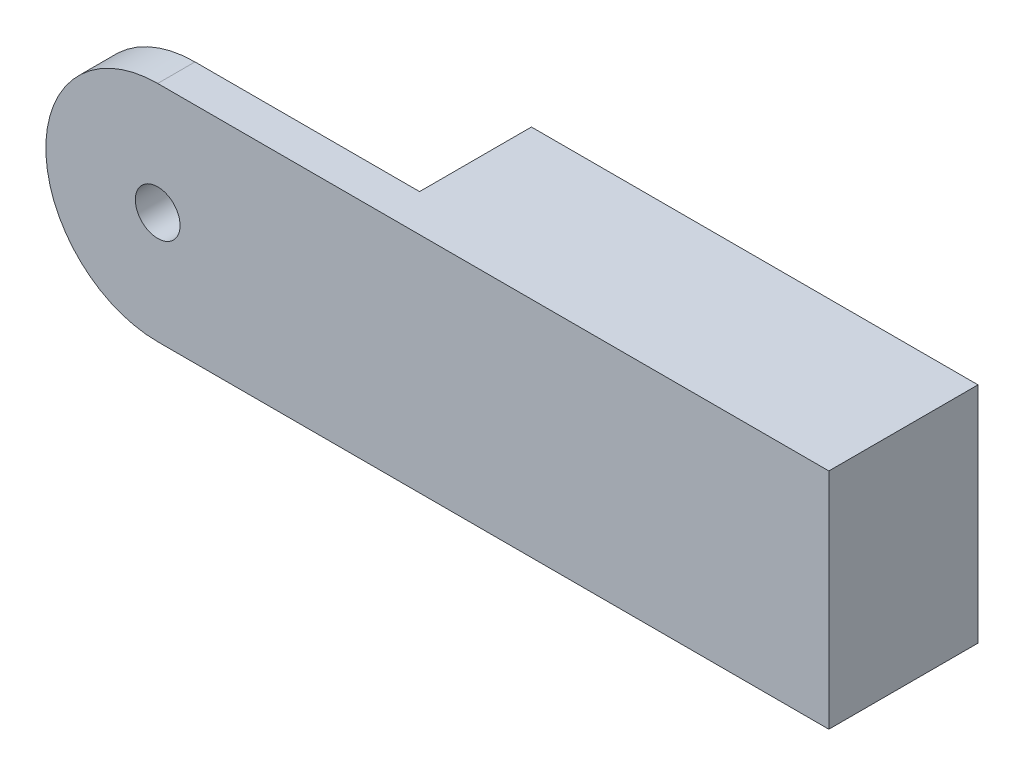
SolidWorks part; units mm, degrees
ref_plane "前视基准面" through (0, 0, 0) normal (0, 0, 1) x (1, 0, 0)
ref_plane "上视基准面" through (0, 0, 0) normal (0, 1, 0) x (1, 0, 0)
ref_plane "右视基准面" through (0, 0, 0) normal (1, 0, 0) x (0, 0, -1)
sketch "草图1" plane through (0, 0, 0) normal (0, 0, 1) x (1, 0, 0)
  line L1 (-45, 15) -> (45, 15)
  line L3 (-45, -15) -> (45, -15)
  line L4 (45, 15) -> (45, -15)
  arc A0 (-45, 15) -> (-45, -15) centre (-45, 0) ccw
  circle A1 centre (-45, 0) radius 3
  point P0 (0, 0)
  dimension "D1" = 30
extrude "凸台-拉伸1" add sketch "草图1" along normal blind 20
ref_plane "基准面1" through (0, 0, 15) normal (0, 0, 1) x (1, 0, 0)
sketch "草图2" plane through (0, 0, 15) normal (0, 0, 1) x (1, 0, 0)
  line L0 (45, 15) -> (-45, 15) construction
  line L1 (-29.6441, 15) -> (-61.6301, 15)
  line L2 (-29.6441, 15) -> (-29.6441, -15)
  line L3 (-29.6441, -15) -> (-61.6301, -15)
  line L4 (-61.6301, 15) -> (-61.6301, -15)
extrude "切除-拉伸2" cut sketch "草图2" against normal through all
sketch "草图3" plane through (0, 0, 15) normal (0, 0, 1) x (1, 0, 0)
  line L0 (45, 15) -> (-29.6441, 15) construction
  line L1 (-14.884, 15) -> (-59.884, 15)
  line L2 (-14.884, 15) -> (-14.884, -15)
  line L3 (-14.884, -15) -> (-59.884, -15)
  line L4 (-59.884, 15) -> (-59.884, -15)
  dimension "D1" = 45
extrude "切除-拉伸3" cut sketch "草图3" against normal through all
ref_axis "基准轴Hand" through (-45, 0, 20) along (0, 0, -1)
sketch "草图4" plane through (0, 0, 15) normal (0, 0, 1) x (1, 0, 0)
  line L0 (-34.2602, 0) -> (-55.744, 0) construction
  line L1 (-45, 10.3516) -> (-45, -10.3516) construction
  point P3 (-45.0021, 0)
  point P8 (-45, 0)
